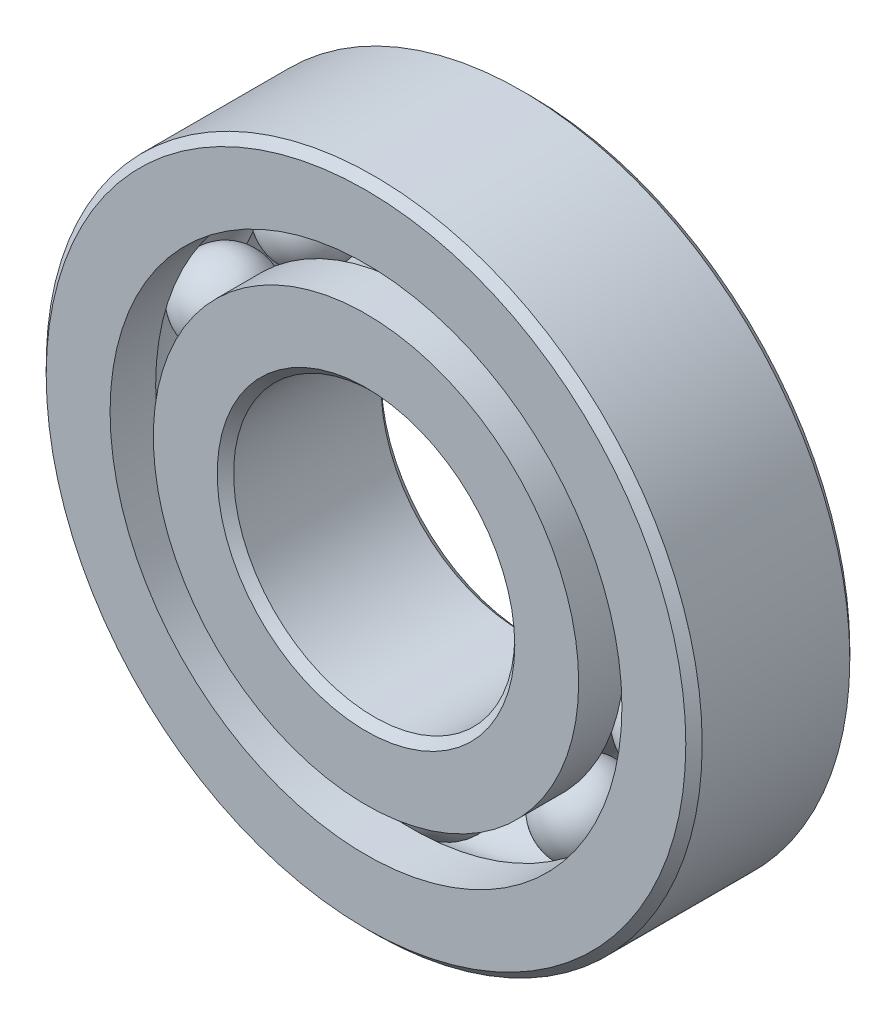
SolidWorks part; units mm, degrees
material "Cast Alloy Steel"
ref_plane "Front Plane" through (0, 0, 0) normal (0, 0, 1) x (1, 0, 0)
ref_plane "Top Plane" through (0, 0, 0) normal (0, 1, 0) x (1, 0, 0)
ref_plane "Right Plane" through (0, 0, 0) normal (1, 0, 0) x (0, 0, -1)
sketch "Sketch1" plane through (0, 0, 0) normal (1, 0, 0) x (0, 0, -1)
  line L0 (-2.7781, 0) -> (2.7781, 0) construction
  line L1 (0, 11.1125) -> (0, -11.1125) construction
  line L2 (2.5003, 11.1125) -> (-2.5003, 11.1125)
  line L3 (-2.5003, 11.1125) -> (-2.7781, 10.8347)
  line L4 (-2.7781, 10.8347) -> (-2.7781, 8.6702)
  line L5 (-2.7781, 8.6702) -> (-1.2347, 8.6702)
  line L6 (2.7781, 8.6702) -> (1.2347, 8.6702)
  line L7 (2.7781, 10.8347) -> (2.7781, 8.6702)
  line L8 (2.5003, 11.1125) -> (2.7781, 10.8347)
  line L9 (0, 11.1125) -> (0, 7.9375) construction
  line L10 (0, 7.9375) -> (0, 4.7625) construction
  arc A0 (-1.2347, 8.6702) -> (1.2347, 8.6702) centre (0, 7.9375) cw
  point P14 (0, 4.7625)
  dimension "D3" = 2.4694
  dimension "D1" = 45
  dimension "Width" = 5.5562
  dimension "OD" = 22.225
  dimension "D2" = 0.2778
  dimension "Shaft Dia" = 9.525
  dimension "D4" = 0.7327
revolve "Revolve1" add sketch "Sketch1" angle 360 about L0
sketch "Sketch3" plane through (0, 0, 0) normal (1, 0, 0) x (0, 0, -1)
  line L0 (-2.7781, 7.2048) -> (-1.2347, 7.2048)
  line L1 (0, 11.1125) -> (0, -11.1125) construction
  line L2 (-2.7781, 10.8347) -> (-2.7781, 8.6702) construction
  line L3 (-2.7781, 7.2048) -> (-2.7781, 5.0403)
  line L4 (-2.5003, 11.1125) -> (-2.7781, 10.8347) construction
  line L5 (-2.7781, 5.0403) -> (-2.5003, 4.7625)
  line L6 (-2.5003, 4.7625) -> (2.5003, 4.7625)
  line L7 (2.5003, 11.1125) -> (2.5003, -11.1125) construction
  line L8 (2.5003, 4.7625) -> (2.7781, 5.0403)
  line L9 (2.7781, -10.8347) -> (2.7781, 10.8347) construction
  line L10 (2.7781, 5.0403) -> (2.7781, 7.2048)
  line L11 (2.7781, 7.2048) -> (1.2347, 7.2048)
  line L13 (2.5003, 11.1125) -> (2.7781, 10.8347) construction
  arc A0 (1.2347, 8.6702) -> (-1.2347, 8.6702) centre (0, 7.9375) ccw construction
  arc A1 (1.2347, 7.2048) -> (-1.2347, 7.2048) centre (0, 7.9375) cw
revolve "Revolve3" add sketch "Sketch3" angle 360 about L0
sketch "Sketch4" plane through (0, 0, 0) normal (1, 0, 0) x (0, 0, -1)
  line L0 (-1.4357, 7.9375) -> (1.4357, 7.9375)
  arc A2 (-1.4357, 7.9375) -> (1.4357, 7.9375) centre (0, 7.9375) cw
  arc A3 (1.2347, 8.6702) -> (-1.2347, 8.6702) centre (0, 7.9375) ccw construction
revolve "Revolve4" add sketch "Sketch4" angle 360 about L0
ref_axis "Axis1" through (0, 0, -2.7781) along (0, 0, 1)
pattern_circular "CirPattern1" count 10 every 36 about axis through (0, 0, -2.7781) along (0, 0, 1) of bodies 104
sketch "Sketch5" plane through (0, 0, 0) normal (1, 0, 0) x (0, 0, -1)
  line L0 (-2.7781, 8.6702) -> (-1.2347, 8.6702) construction
  line L1 (-2.6392, 8.6702) -> (-1.4357, 8.6702)
  line L2 (-2.6392, 8.6702) -> (-2.6392, 7.2048)
  line L3 (-2.6392, 7.2048) -> (-1.4357, 7.2048)
  line L4 (-1.4357, 8.6702) -> (-1.4357, 7.2048)
  line L5 (-2.7781, 7.2048) -> (-1.2347, 7.2048) construction
  line L6 (2.7781, 8.6702) -> (1.2347, 8.6702) construction
  line L7 (2.6392, 8.6702) -> (1.4357, 8.6702)
  line L8 (2.6392, 8.6702) -> (2.6392, 7.2048)
  line L9 (2.6392, 7.2048) -> (1.4357, 7.2048)
  line L10 (1.4357, 8.6702) -> (1.4357, 7.2048)
  line L11 (2.7781, 7.2048) -> (1.2347, 7.2048) construction
  line L12 (-2.5003, 11.1125) -> (-2.7781, 10.8347) construction
  point P18 (-2.6392, 10.9736)
revolve "Revolve5" [suppressed] add sketch "Sketch5" angle 360 about L0
equation "\"D2@Sketch1\" = \"Width@Sketch1\"*.05"
equation "\"D3@Sketch1\" = \"Width@Sketch1\"/2.25"
equation "\"D4@Sketch1\" = (((\"OD@Sketch1\"-\"Width@Sketch1\")/2)/3.25)/3.5"
equation "\"D2@CirPattern1\" = 360/\"Balls@CirPattern1\""
